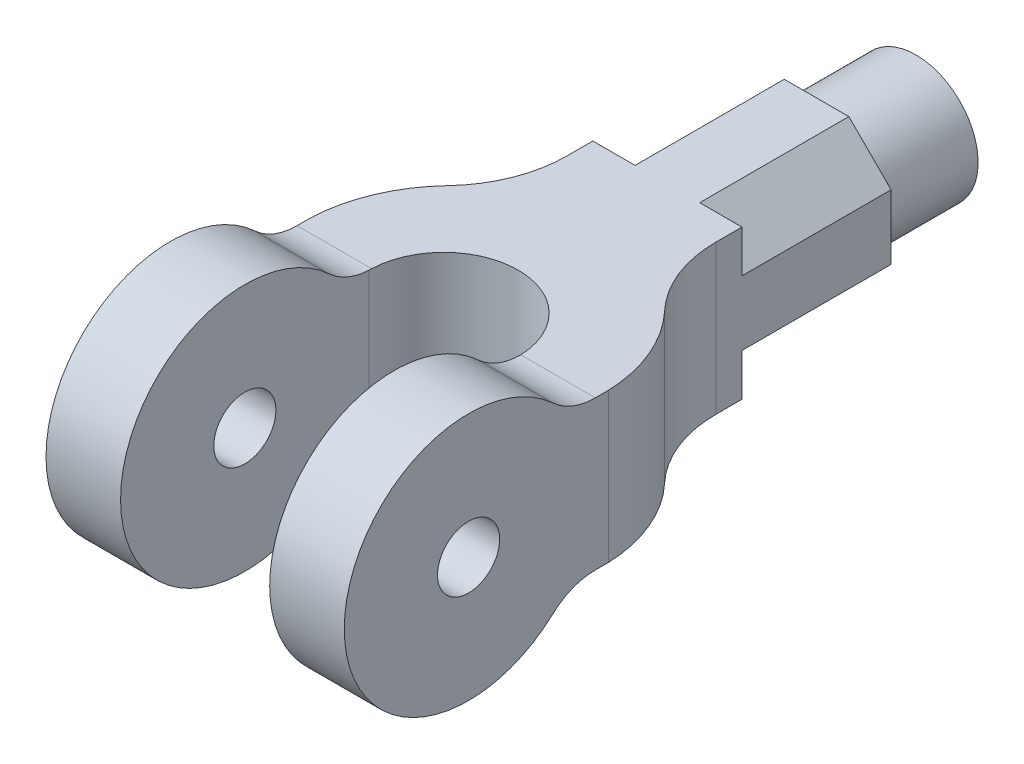
SolidWorks part; units mm, degrees
ref_plane "Front Plane" through (0, 0, 0) normal (0, 0, 1) x (1, 0, 0)
ref_plane "Top Plane" through (0, 0, 0) normal (0, 1, 0) x (1, 0, 0)
ref_plane "Right Plane" through (0, 0, 0) normal (1, 0, 0) x (0, 0, -1)
sketch "Sketch1" plane through (0, 0, 0) normal (0, 1, 0) x (1, 0, 0)
  line L1 (0, 0) -> (-120, 0)
  line L2 (0, 0) -> (0, 250)
  line L3 (0, 250) -> (-120, 250)
  line L4 (-120, 0) -> (-120, 250)
  dimension "D1" = 120
  dimension "D2" = 250
extrude "Boss-Extrude2" add sketch "Sketch1" along normal blind 100
sketch "Sketch4" plane through (0, 100, 0) normal (0, 1, 0) x (1, 0, 0)
  line L0 (-60, 250) -> (-60, 0) construction
  line L1 (0, 250) -> (-120, 250) construction
  line L2 (-120, 0) -> (0, 0) construction
  line L3 (-90, 250) -> (-90, 179.5616)
  line L4 (-30, 250) -> (-30, 179.5616)
  line L5 (-90, 100) -> (-90, 0)
  line L6 (-30, 100) -> (-30, 0)
  arc A0 (-30, 100) -> (-90, 100) centre (-60, 100) ccw
  arc A1 (-103.6507, 145.229) -> (-16.3493, 145.229) centre (-60, 104) ccw
  arc A2 (-16.3493, 145.229) -> (-30, 179.5616) centre (20, 179.5616) cw
  arc A3 (-103.6507, 145.229) -> (-90, 179.5616) centre (-140, 179.5616) ccw
  point P15 (-30, 156.0117)
  point P18 (-90, 156.0117)
  line M6 (0, 0) -> (0, 250)
  line M7 (0, 250) -> (-120, 250)
  line M8 (-120, 250) -> (-120, 0)
  line M9 (-120, 0) -> (0, 0)
  dimension "D1" = 60
  dimension "D5" = 50
  dimension "D2" = 4
  dimension "D3" = 150
  dimension "D4" = 30
extrude "Cut-Extrude1" cut sketch "Sketch4" against normal through all contours A1 L0 L6 M9 | L0 A1 L5 M9 | A0 L0 A1 L6 | L0 A0 L5 A1 | A2 A1 L4 M6 M7 | A1 A3 L3 M7 M8 region at (-45.9507, 100, -85.3146) region at (-74.0493, 100, -85.3146) region at (-13.8275, 100, -195.5544) region at (-106.1725, 100, -195.5544) region at (-44.5752, 100, -23.3392) region at (-75.4248, 100, -23.3392)
sketch "Sketch5" plane through (0, 0, 0) normal (1, 0, 0) x (0, 0, -1)
  line L0 (0, 100) -> (106.2831, 100) construction
  line L1 (0, 100) -> (0, 0) construction
  line L2 (0, 0) -> (106.2831, 0) construction
  line L3 (50, 50) -> (250, 50) construction
  line L4 (250, 0) -> (250, 100) construction
  line L5 (0, 100) -> (106.2831, 100)
  line L6 (100.9902, 80) -> (250, 80)
  line L8 (100.9902, 20) -> (250, 20)
  line L9 (250, 80) -> (250, 20)
  line L10 (106.2831, 100) -> (250, 100)
  line L11 (250, 100) -> (250, 80)
  line L12 (250, 0) -> (179.5616, 0)
  line L13 (250, 20) -> (250, 0)
  line L14 (179.5616, 0) -> (145.229, 0)
  line L15 (0, 0) -> (0, 100)
  line L16 (145.229, 0) -> (106.2831, 0)
  line L17 (106.2831, 0) -> (0, 0)
  arc A0 (83.9935, 86.6667) -> (83.9935, 13.3333) centre (50, 50) ccw
  circle A1 centre (50, 50) radius 12.5
  arc A2 (83.9935, 13.3333) -> (100.9902, 20) centre (100.9902, -5) cw
  arc A3 (100.9902, 80) -> (83.9935, 86.6667) centre (100.9902, 105) cw
  line M10 (106.2831, 0) -> (106.2831, 100)
  line M11 (106.2831, 100) -> (0, 100)
  line M12 (0, 100) -> (0, 0)
  line M13 (0, 0) -> (106.2831, 0)
  dimension "D1" = 25
  dimension "D4" = 25
  dimension "D2" = 60
  dimension "D3" = 30
extrude "Cut-Extrude3" cut sketch "Sketch5" against normal through all contours A0 L5 M12 | A1 | A0 L15 M13 | A2 A0 L17 L8 M10 | L16 L14 L12 L13 L8 M10 | A3 L6 A0 M10 M11 | L11 L10 L6 M10 region at (0, 88.8316, -11.1684) region at (0, 92.0889, -90.602) region at (0, 11.1684, -11.1684) region at (0, 90, -178.1415) region at (0, 7.9111, -90.602) region at (0, 10, -178.1415) region at (0, 50, -50)
sketch "Sketch6" plane through (0, 0, -250) normal (0, 0, -1) x (-1, 0, 0)
  line L0 (90, 80) -> (30, 20) construction
  line L1 (90, 63) -> (90, 80)
  line L2 (90, 20) -> (90, 80) construction
  line L3 (73, 80) -> (90, 63)
  line L4 (90, 80) -> (30, 80) construction
  line L5 (73, 80) -> (90, 80)
  line L6 (90, 37) -> (73, 20)
  line L7 (90, 37) -> (90, 20)
  line L8 (73, 20) -> (90, 20)
  line L9 (47, 20) -> (30, 37)
  line L10 (47, 20) -> (30, 20)
  line L11 (30, 37) -> (30, 20)
  line L12 (30, 63) -> (47, 80)
  line L13 (30, 63) -> (30, 80)
  line L14 (47, 80) -> (30, 80)
  circle A0 centre (60, 50) radius 25
  line M8 (30, 20) -> (90, 20)
  line M9 (90, 20) -> (90, 80)
  line M10 (90, 80) -> (30, 80)
  line M11 (30, 80) -> (30, 20)
  dimension "D1" = 50
  dimension "D2" = 17
  dimension "D3" = 17
  dimension "D4" = 4
extrude "Cut-Extrude4" cut sketch "Sketch6" against normal blind 60 contours L12 M11 M10 | L0 L3 M10 | L0 L3 M9 | L6 M9 M8 | L0 L9 M11 | L9 L0 M8 region at (-87.1667, 71.5, -250) region at (-81.5, 77.1667, -250) region at (-84.3333, 25.6667, -250) region at (-35.6667, 74.3333, -250) region at (-38.5, 22.8333, -250) region at (-32.8333, 28.5, -250)
extrude "Boss-Extrude3" add sketch "Sketch6<3>" along normal blind 40 contours L0 A0 | A0 L0 region at (-67.5026, 42.4974, -250) region at (-52.4974, 57.5026, -250)
sketch "Sketch6<3>" plane through (0, 0, -250) normal (0, 0, -1) x (-1, 0, 0) same geometry as "Sketch6"
